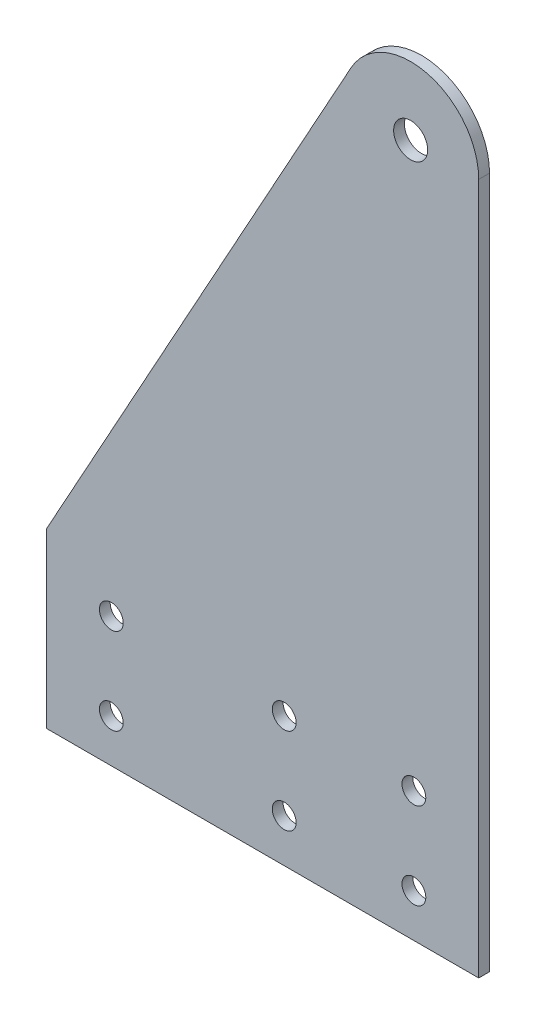
SolidWorks part; units mm, degrees
ref_plane "Front Plane" through (0, 0, 0) normal (0, 0, 1) x (1, 0, 0)
ref_plane "Top Plane" through (0, 0, 0) normal (0, 1, 0) x (1, 0, 0)
ref_plane "Right Plane" through (0, 0, 0) normal (1, 0, 0) x (0, 0, -1)
sketch "Sketch1" plane through (0, 0, 0) normal (0, 0, 1) x (1, 0, 0)
  line L0 (-63.5, -25.4) -> (63.5, -25.4)
  line L2 (63.5, -25.4) -> (63.5, 177.8)
  line L3 (25.9919, 187.4678) -> (-63.5, 25.4)
  line L5 (-63.5, 25.4) -> (-63.5, -25.4)
  line L6 (-63.5, 25.4) -> (63.5, -25.4) construction
  line L7 (44.45, 12.7) -> (6.35, 12.7) construction
  line L8 (-44.45, -12.7) -> (44.45, -12.7) construction
  line L9 (-44.45, -12.7) -> (-44.45, 12.7) construction
  line L10 (-44.45, 12.7) -> (44.45, 12.7) construction
  line L11 (44.45, -12.7) -> (44.45, 12.7) construction
  line L12 (-44.45, -12.7) -> (44.45, 12.7) construction
  line L13 (-44.45, 12.7) -> (44.45, -12.7) construction
  arc A0 (25.9919, 187.4678) -> (63.5, 177.8) centre (43.5, 177.8) cw
  circle A1 centre (43.5, 177.8) radius 5
  circle A2 centre (-44.45, 12.7) radius 3.5
  circle A3 centre (44.45, 12.7) radius 3.5
  circle A4 centre (44.45, -12.7) radius 3.5
  circle A5 centre (-44.45, -12.7) radius 3.5
  circle A6 centre (6.35, 12.7) radius 3.5
  circle A7 centre (6.35, -12.7) radius 3.5
  point P7 (0, 0)
  point P8 (0, 0)
  dimension "D2" = 10
  dimension "D6" = 20
  dimension "D5" = 7
  dimension "D1" = 50.8
  dimension "D3" = 127
  dimension "D4" = 152.4
  dimension "D7" = 25.4
  dimension "D8" = 88.9
  dimension "D9" = 38.1
extrude "Boss-Extrude1" add sketch "Sketch1" along normal blind 3.175
